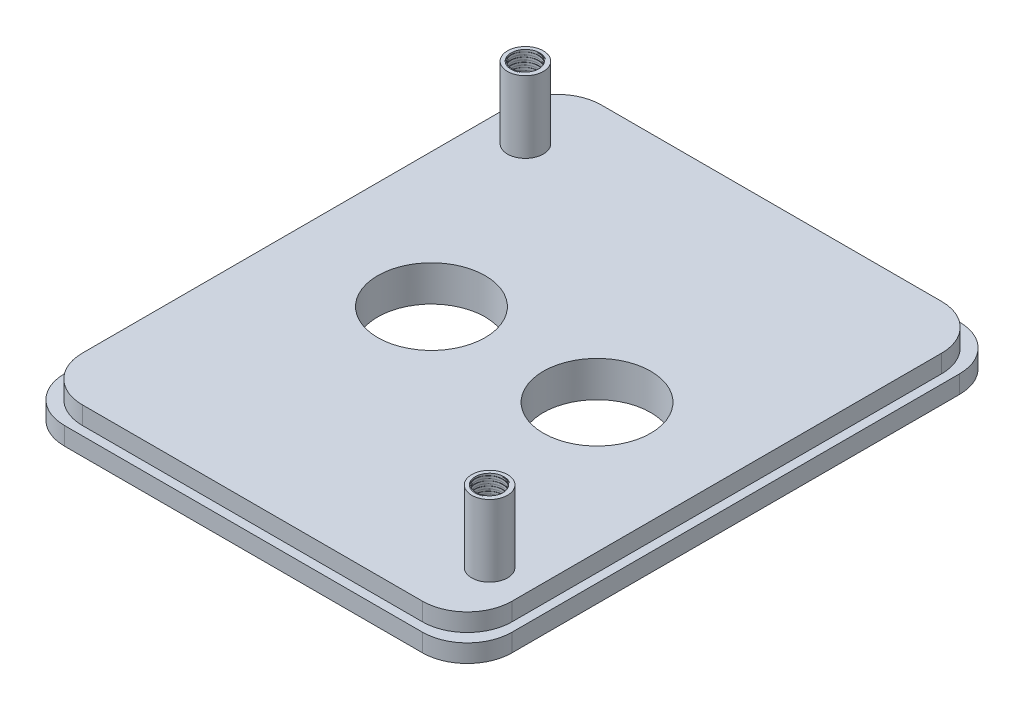
SolidWorks part; units mm, degrees
material "ABS"
ref_plane "Alzado" through (0, 0, 0) normal (0, 0, 1) x (1, 0, 0)
ref_plane "Planta" through (0, 0, 0) normal (0, 1, 0) x (1, 0, 0)
ref_plane "Vista lateral" through (0, 0, 0) normal (1, 0, 0) x (0, 0, -1)
sketch "Croquis1" plane through (0, 0, 0) normal (0, 1, 0) x (1, 0, 0)
  line L1 (-25, 30) -> (25, 30)
  line L2 (-25, 30) -> (-25, -30)
  line L3 (-25, -30) -> (25, -30)
  line L4 (25, 30) -> (25, -30)
  line L5 (-25, 30) -> (25, -30) construction
  line L6 (-25, -30) -> (25, 30) construction
  point P0 (0, 0)
  dimension "D1" = 50
  dimension "D2" = 60
extrude "Saliente-Extruir1" add sketch "Croquis1" along normal blind 2
sketch "Croquis2" plane through (0, 2, 0) normal (0, 1, 0) x (1, 0, 0)
  line L0 (-25, 30) -> (-25, -30) construction
  line L1 (24, -29) -> (-24, -29)
  line L2 (24, -29) -> (24, 29)
  line L3 (24, 29) -> (-24, 29)
  line L4 (-24, -29) -> (-24, 29)
  line L5 (24, -29) -> (-24, 29) construction
  line L6 (24, 29) -> (-24, -29) construction
  line L7 (-25, -30) -> (25, -30) construction
  point P0 (0, 0)
  dimension "D1" = 1
  dimension "D2" = 1
extrude "Saliente-Extruir2" add sketch "Croquis2" along normal blind 2
sketch "Croquis3" plane through (0, 4, 0) normal (0, 1, 0) x (1, 0, 0)
  line L3 (-22.5, -25) -> (22.5, -25)
  line L4 (22.5, 25) -> (22.5, -25)
  line L5 (-22.5, 25) -> (22.5, -25) construction
  line L6 (-22.5, -25) -> (22.5, 25) construction
  circle A0 centre (-19.5, 21) radius 2
  circle A1 centre (19.5, -22) radius 2
  point P0 (0, 0)
  dimension "D1" = 45
  dimension "D2" = 50
  dimension "D4" = 46
  dimension "D6" = 3
extrude "Saliente-Extruir5" add sketch "Croquis3" along normal blind 2 contours A0 | A1
sketch "Croquis4" plane through (0, 0, 0) normal (0, -1, 0) x (1, 0, 0)
  line L0 (0, -25) -> (0, -13.066) construction
  line L1 (22.5, -25) -> (-22.5, -25)
  line L3 (22.5, 25) -> (-22.5, 25)
  line L4 (-22.5, 25) -> (-22.5, -25)
  line L5 (22.5, -25) -> (-22.5, 25) construction
  line L6 (22.5, 25) -> (-22.5, -25) construction
  circle A0 centre (-9, 0) radius 6
  circle A1 centre (9.5, 0) radius 6
  point P0 (0, 0)
  dimension "D3" = 9
  dimension "D6" = 12
  dimension "D1" = 50
  dimension "D2" = 45
  dimension "D4" = 25
  dimension "D5" = 9.5
extrude "Cortar-Extruir10" cut sketch "Croquis4" against normal blind 5 contours A0 | A1
sketch "Croquis5" plane through (0, 6, 0) normal (0, 1, 0) x (1, 0, 0)
  circle A0 centre (-19.5, 21) radius 2
  circle A1 centre (19.5, -22) radius 2
extrude "Saliente-Extruir7" add sketch "Croquis5" along normal blind 6
sketch "Croquis6" plane through (0, 12, 0) normal (0, 1, 0) x (1, 0, 0)
  circle A0 centre (19.5, -22) radius 1.5
  circle A1 centre (-19.5, 21) radius 1.5
extrude "Cortar-Extruir11" cut sketch "Croquis6" against normal blind 5
sketch "Croquis7" plane through (0, 12, 0) normal (0, 1, 0) x (1, 0, 0)
  circle A0 centre (-19.5, 21) radius 1.5
curve "Hélice/Espiral1" pitch 0.5 height 6 turns 12
ref_plane "Plano2" through (0, 6, 0) normal (0, 1, 0) x (1, 0, 0)
ref_plane "Plano5" through (0, 0, -21) normal (0, 0, 1) x (1, 0, 0)
sketch "Croquis15" plane through (0, 0, -21) normal (0, 0, 1) x (1, 0, 0)
  line L0 (-17.5, 12) -> (-21.5, 12) construction
  line L1 (-20.8, 12) -> (-21.1, 12.1732)
  line L2 (-21.1, 12.1732) -> (-21.1, 11.8268)
  line L3 (-21.1, 11.8268) -> (-20.8, 12)
  line L4 (-18, 12) -> (-21, 12) construction
  circle A0 centre (-21, 12) radius 0.1 construction
sweep "Cortar-Barrer2" cut profiles "Croquis15" path "Hélice/Espiral1"
sketch "Croquis16" plane through (0, 12, 0) normal (0, 1, 0) x (1, 0, 0)
  circle A0 centre (19.5, -22) radius 1.5
curve "Hélice/Espiral2" pitch 0.5 height 6 turns 12
ref_plane "Plano8" through (0, 0, 22) normal (0, 0, 1) x (1, 0, 0)
sketch "Croquis18" plane through (0, 0, 22) normal (0, 0, 1) x (1, 0, 0)
  line L1 (18.2, 12) -> (17.9, 12.1732)
  line L2 (17.9, 12.1732) -> (17.9, 11.8268)
  line L3 (17.9, 11.8268) -> (18.2, 12)
  circle A0 centre (18, 12) radius 0.1 construction
sweep "Cortar-Barrer4" cut profiles "Croquis18" path "Hélice/Espiral2"
sketch "Croquis19" plane through (0, 0, 0) normal (0, -1, 0) x (1, 0, 0)
  line L0 (-9, -6) -> (-9, -12) construction
  line L1 (-3, -12) -> (-15, -12) construction
  circle A0 centre (-9, 0) radius 6 construction
  text T0 "ABRIR"
  dimension "D1" = 12
  dimension "D2" = 6
extrude "Cortar-Extruir12" cut sketch "Croquis19" against normal blind 0.1
sketch "Croquis22" plane through (0, 0, 0) normal (0, -1, 0) x (1, 0, 0)
  text T0 "CERRAR"
extrude "Cortar-Extruir14" cut sketch "Croquis22" against normal blind 0.1
fillet "Redondeo1" radius 5 2 edges at (24, 3, -29) (25, 1, -30)
fillet "Redondeo2" radius 5 6 edges at (25, 1, 30) (24, 3, 29) (-24, 3, 29) (-25, 1, 30) (-24, 3, -29) (-25, 1, -30)
sketch "Croquis23" plane through (0, 0, 0) normal (0, -1, 0) x (1, 0, 0)
  text T0 "SMART HOUSE & CO" font "Century Gothic" height in points 10
extrude "Cortar-Extruir15" cut sketch "Croquis23" against normal blind 0.1
